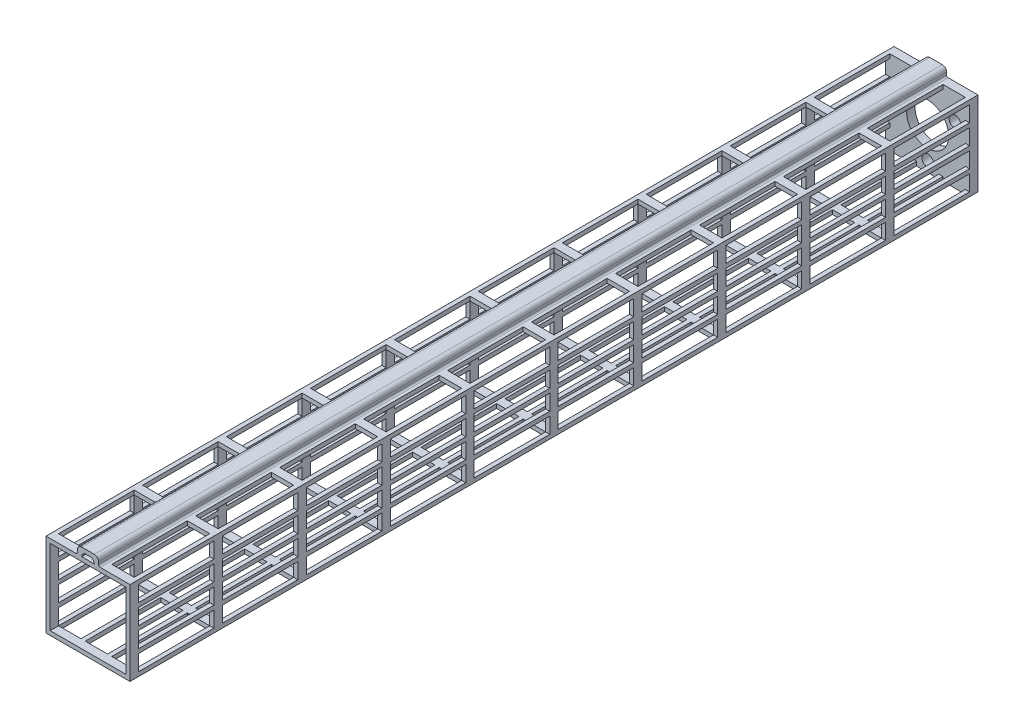
SolidWorks part; units mm, degrees
ref_plane "Front Plane" through (0, 0, 0) normal (0, 0, 1) x (1, 0, 0)
ref_plane "Top Plane" through (0, 0, 0) normal (0, 1, 0) x (1, 0, 0)
ref_plane "Right Plane" through (0, 0, 0) normal (1, 0, 0) x (0, 0, -1)
sketch "Sketch1" plane through (0, 0, 0) normal (0, 0, 1) x (1, 0, 0)
  line L0 (0, 14.5892) -> (0, -5.317) construction
  line L1 (-12.7, -12.7) -> (12.7, -12.7)
  line L2 (12.7, -12.7) -> (12.7, 12.7)
  line L3 (12.7, 12.7) -> (3.175, 12.7)
  line L4 (3.175, 12.7) -> (3.175, 15.24)
  line L5 (3.175, 15.24) -> (-3.175, 15.24)
  line L6 (-12.7, -12.7) -> (-12.7, 12.7)
  line L7 (-3.175, 12.7) -> (-3.175, 15.24)
  line L8 (-12.7, 12.7) -> (-3.175, 12.7)
  circle A0 centre (0, 0) radius 6.35 construction
  circle A1 centre (0, 0) radius 12.7 construction
  circle A2 centre (0, 0) radius 9.525 construction
  circle A3 centre (0, -9.525) radius 1.778
  circle A4 centre (-8.2489, 4.7625) radius 1.778
  circle A5 centre (8.2489, 4.7625) radius 1.778
  circle A6 centre (0, 0) radius 6.35
  point P13 (0, 0)
  point P22 (0, -12.7)
  point P25 (0, 15.24)
  dimension "D1" = 12.7
  dimension "D2" = 25.4
  dimension "D3" = 19.05
  dimension "D4" = 3.556
  dimension "D6" = 9.525
  dimension "D7" = 25.4
  dimension "D8" = 12.7
  dimension "D9" = 12.7
  dimension "D10" = 2.54
  dimension "D5" = 3
extrude "Boss-Extrude1" add sketch "Sketch1" along normal blind 2.54
sketch "Sketch6" plane through (0, 0, 2.54) normal (0, 0, 1) x (1, 0, 0)
  line L0 (-12.7, -12.7) -> (12.7, -12.7) construction
  line L1 (12.7, -12.7) -> (12.7, 12.7) construction
  line L2 (12.7, 12.7) -> (3.175, 12.7) construction
  line L3 (3.175, 12.7) -> (3.175, 15.24) construction
  line L4 (3.175, 15.24) -> (-3.175, 15.24) construction
  line L5 (-3.175, 15.24) -> (-3.175, 12.7) construction
  line L6 (-12.7, 12.7) -> (-12.7, -12.7) construction
  line L7 (-3.175, 12.7) -> (-12.7, 12.7) construction
  line L8 (-12.7, -12.7) -> (12.7, -12.7)
  line L9 (12.7, -12.7) -> (12.7, 12.7)
  line L10 (12.7, 12.7) -> (3.175, 12.7)
  line L11 (3.175, 12.7) -> (3.175, 15.24)
  line L12 (3.175, 15.24) -> (-3.175, 15.24)
  line L13 (-3.175, 15.24) -> (-3.175, 12.7)
  line L14 (-12.7, 12.7) -> (-12.7, -12.7)
  line L15 (-3.175, 12.7) -> (-12.7, 12.7)
  line L17 (-11.43, 11.43) -> (11.43, 11.43)
  line L18 (-11.43, 11.43) -> (-11.43, -11.43)
  line L19 (-11.43, -11.43) -> (11.43, -11.43)
  line L20 (11.43, 11.43) -> (11.43, -11.43)
  dimension "D1" = 1.27
  dimension "D2" = 1.27
  dimension "D3" = 1.27
  dimension "D4" = 1.27
extrude "Boss-Extrude5" [suppressed] add sketch "Sketch6" along normal blind 254
sketch "Sketch2" plane through (0, 0, 2.54) normal (0, 0, 1) x (1, 0, 0)
  line L0 (-11.43, 11.43) -> (-11.43, -11.43) construction
  line L1 (-11.43, -11.43) -> (11.43, -11.43) construction
  line L2 (11.43, -11.43) -> (11.43, 11.43) construction
  line L3 (11.43, 11.43) -> (-11.43, 11.43) construction
  line L4 (-12.7, 12.7) -> (-12.7, -12.7) construction
  line L5 (-4.6567, 12.7) -> (-3.3867, 12.7)
  line L6 (-12.7, -12.7) -> (12.7, -12.7) construction
  line L7 (12.7, -12.7) -> (12.7, 12.7) construction
  line L8 (12.7, 12.7) -> (3.175, 12.7) construction
  line L9 (3.175, 12.7) -> (3.175, 15.24) construction
  line L10 (3.175, 15.24) -> (-3.175, 15.24) construction
  line L11 (-3.175, 15.24) -> (-3.175, 12.7) construction
  line L12 (-3.175, 12.7) -> (-12.7, 12.7) construction
  line L13 (-12.7, -12.7) -> (12.7, -12.7) construction
  line L14 (12.7, -12.7) -> (12.7, 12.7) construction
  line L15 (12.7, 12.7) -> (3.175, 12.7) construction
  line L16 (3.175, 12.7) -> (3.175, 15.24) construction
  line L17 (3.175, 15.24) -> (-3.175, 15.24) construction
  line L18 (-3.175, 15.24) -> (-3.175, 12.7) construction
  line L19 (-3.175, 12.7) -> (-12.7, 12.7) construction
  line L20 (-12.7, 12.7) -> (-12.7, -12.7) construction
  line L21 (-12.7, 12.7) -> (-11.43, 12.7)
  line L22 (-12.7, 12.7) -> (-12.7, 11.43)
  line L23 (-12.7, 11.43) -> (-11.43, 11.43)
  line L24 (-11.43, 12.7) -> (-11.43, 11.43)
  line L34 (-4.6567, 11.43) -> (-3.3867, 11.43)
  line L35 (-4.6567, 12.7) -> (-4.6567, 11.43)
  line L36 (3.3867, 12.7) -> (4.6567, 12.7)
  line L37 (4.6567, 12.7) -> (4.6567, 11.43)
  line L38 (3.3867, 11.43) -> (4.6567, 11.43)
  line L40 (11.43, 12.7) -> (12.7, 12.7)
  line L41 (12.7, 12.7) -> (12.7, 11.43)
  line L42 (11.43, 11.43) -> (12.7, 11.43)
  line L43 (11.43, 12.7) -> (11.43, 11.43)
  line L44 (-4.6567, 6.6675) -> (-3.3867, 6.6675) [skipped]
  line L45 (-3.3867, 6.6675) -> (-3.3867, 5.3975) [skipped]
  line L46 (-4.6567, 5.3975) -> (-3.3867, 5.3975) [skipped]
  line L47 (-4.6567, 6.6675) -> (-4.6567, 5.3975) [skipped]
  line L48 (3.3867, 6.6675) -> (4.6567, 6.6675) [skipped]
  line L49 (4.6567, 6.6675) -> (4.6567, 5.3975) [skipped]
  line L50 (3.3867, 5.3975) -> (4.6567, 5.3975) [skipped]
  line L51 (3.3867, 6.6675) -> (3.3867, 5.3975) [skipped]
  line L52 (11.43, 6.6675) -> (12.7, 6.6675)
  line L53 (12.7, 6.6675) -> (12.7, 5.3975)
  line L54 (11.43, 5.3975) -> (12.7, 5.3975)
  line L55 (11.43, 6.6675) -> (11.43, 5.3975)
  line L56 (-4.6567, 0.635) -> (-3.3867, 0.635) [skipped]
  line L57 (-3.3867, 0.635) -> (-3.3867, -0.635) [skipped]
  line L58 (-4.6567, -0.635) -> (-3.3867, -0.635) [skipped]
  line L59 (-4.6567, 0.635) -> (-4.6567, -0.635) [skipped]
  line L60 (3.3867, 0.635) -> (4.6567, 0.635) [skipped]
  line L61 (4.6567, 0.635) -> (4.6567, -0.635) [skipped]
  line L62 (3.3867, -0.635) -> (4.6567, -0.635) [skipped]
  line L63 (3.3867, 0.635) -> (3.3867, -0.635) [skipped]
  line L64 (11.43, 0.635) -> (12.7, 0.635)
  line L65 (12.7, 0.635) -> (12.7, -0.635)
  line L66 (11.43, -0.635) -> (12.7, -0.635)
  line L67 (11.43, 0.635) -> (11.43, -0.635)
  line L68 (-4.6567, -5.3975) -> (-3.3867, -5.3975) [skipped]
  line L69 (-3.3867, -5.3975) -> (-3.3867, -6.6675) [skipped]
  line L70 (-4.6567, -6.6675) -> (-3.3867, -6.6675) [skipped]
  line L71 (-4.6567, -5.3975) -> (-4.6567, -6.6675) [skipped]
  line L72 (3.3867, -5.3975) -> (4.6567, -5.3975) [skipped]
  line L73 (4.6567, -5.3975) -> (4.6567, -6.6675) [skipped]
  line L74 (3.3867, -6.6675) -> (4.6567, -6.6675) [skipped]
  line L75 (3.3867, -5.3975) -> (3.3867, -6.6675) [skipped]
  line L76 (11.43, -5.3975) -> (12.7, -5.3975)
  line L77 (12.7, -5.3975) -> (12.7, -6.6675)
  line L78 (11.43, -6.6675) -> (12.7, -6.6675)
  line L79 (11.43, -5.3975) -> (11.43, -6.6675)
  line L80 (-4.6567, -11.43) -> (-3.3867, -11.43)
  line L81 (-3.3867, -11.43) -> (-3.3867, -12.7)
  line L82 (-4.6567, -12.7) -> (-3.3867, -12.7)
  line L83 (-4.6567, -11.43) -> (-4.6567, -12.7)
  line L84 (3.3867, -11.43) -> (4.6567, -11.43)
  line L85 (4.6567, -11.43) -> (4.6567, -12.7)
  line L86 (3.3867, -12.7) -> (4.6567, -12.7)
  line L87 (3.3867, -11.43) -> (3.3867, -12.7)
  line L88 (11.43, -11.43) -> (12.7, -11.43)
  line L89 (12.7, -11.43) -> (12.7, -12.7)
  line L90 (11.43, -12.7) -> (12.7, -12.7)
  line L91 (11.43, -11.43) -> (11.43, -12.7)
  line L92 (-12.7, 6.6675) -> (-11.43, 6.6675)
  line L93 (-11.43, 6.6675) -> (-11.43, 5.3975)
  line L94 (-12.7, 5.3975) -> (-11.43, 5.3975)
  line L95 (-12.7, 6.6675) -> (-12.7, 5.3975)
  line L96 (-12.7, 0.635) -> (-11.43, 0.635)
  line L97 (-11.43, 0.635) -> (-11.43, -0.635)
  line L98 (-12.7, -0.635) -> (-11.43, -0.635)
  line L99 (-12.7, 0.635) -> (-12.7, -0.635)
  line L100 (-12.7, -5.3975) -> (-11.43, -5.3975)
  line L101 (-11.43, -5.3975) -> (-11.43, -6.6675)
  line L102 (-12.7, -6.6675) -> (-11.43, -6.6675)
  line L103 (-12.7, -5.3975) -> (-12.7, -6.6675)
  line L104 (-12.7, -11.43) -> (-11.43, -11.43)
  line L105 (-11.43, -11.43) -> (-11.43, -12.7)
  line L106 (-12.7, -12.7) -> (-11.43, -12.7)
  line L107 (-12.7, -11.43) -> (-12.7, -12.7)
  line L108 (-3.3867, 11.43) -> (3.3867, 11.43)
  line L109 (3.3867, 12.7) -> (3.175, 12.7)
  line L110 (3.175, 12.7) -> (3.175, 15.24)
  line L111 (3.175, 15.24) -> (-3.175, 15.24)
  line L112 (-3.175, 15.24) -> (-3.175, 12.7)
  line L113 (-3.175, 12.7) -> (-3.3867, 12.7)
  line L115 (-3.3867, 12.2786) -> (-3.3867, 11.43) [skipped]
  line L116 (3.3867, 12.7) -> (3.3867, 11.43) [skipped]
  dimension "D1" = 22.86
  dimension "D2" = 22.86
  dimension "D3" = 1.27
  dimension "D4" = 1.27
  dimension "D5" = 1.27
  dimension "D6" = 4
  dimension "D7" = 5
extrude "Boss-Extrude2" add sketch "Sketch2" along normal blind 254
fillet "Fillet1" radius 1.27 2 edges at (3.175, 15.24, 128.27) (-3.175, 15.24, 128.27)
fillet "Fillet2" radius 0.508 2 edges at (3.175, 12.7, 128.27) (-3.175, 12.7, 128.27)
sketch "Sketch8" plane through (0, 0, 256.54) normal (0, 0, 1) x (1, 0, 0)
  line L0 (-11.43, 11.43) -> (11.43, 11.43) construction
  line L1 (-1.905, 11.43) -> (1.905, 11.43)
  line L2 (-1.905, 11.43) -> (-1.905, 13.97)
  line L3 (-1.905, 13.97) -> (1.905, 13.97)
  line L4 (1.905, 11.43) -> (1.905, 13.97)
  line L5 (-3.175, 13.97) -> (-3.175, 13.208) construction
  line L6 (1.905, 15.24) -> (-1.905, 15.24) construction
  line L7 (3.175, 13.208) -> (3.175, 13.97) construction
  dimension "D1" = 1.27
  dimension "D2" = 1.27
  dimension "D3" = 1.27
extrude "Cut-Extrude1" cut sketch "Sketch8" against normal through all
sketch "Sketch7" plane through (0, 0, 256.54) normal (0, 0, 1) x (1, 0, 0)
  line L1 (-11.43, 11.43) -> (11.43, 11.43)
  line L2 (-11.43, 11.43) -> (-11.43, -11.43)
  line L3 (-11.43, -11.43) -> (11.43, -11.43)
  line L4 (11.43, 11.43) -> (11.43, -11.43)
  line L5 (12.7, -12.7) -> (-12.7, -12.7)
  line L6 (12.7, -12.7) -> (12.7, 12.7)
  line L7 (12.7, 12.7) -> (-12.7, 12.7)
  line L8 (-12.7, -12.7) -> (-12.7, 12.7)
extrude "Boss-Extrude6" add sketch "Sketch7" against normal blind 2.54
fillet "Fillet3" radius 1.27 4 edges at (-1.905, 11.43, 128.27) (1.905, 11.43, 128.27) (1.905, 13.97, 128.27) (-1.905, 13.97, 128.27)
pattern_linear "LPattern1" count 10 spacing 25.4 along (0, 0, -1) of "Boss-Extrude6"
